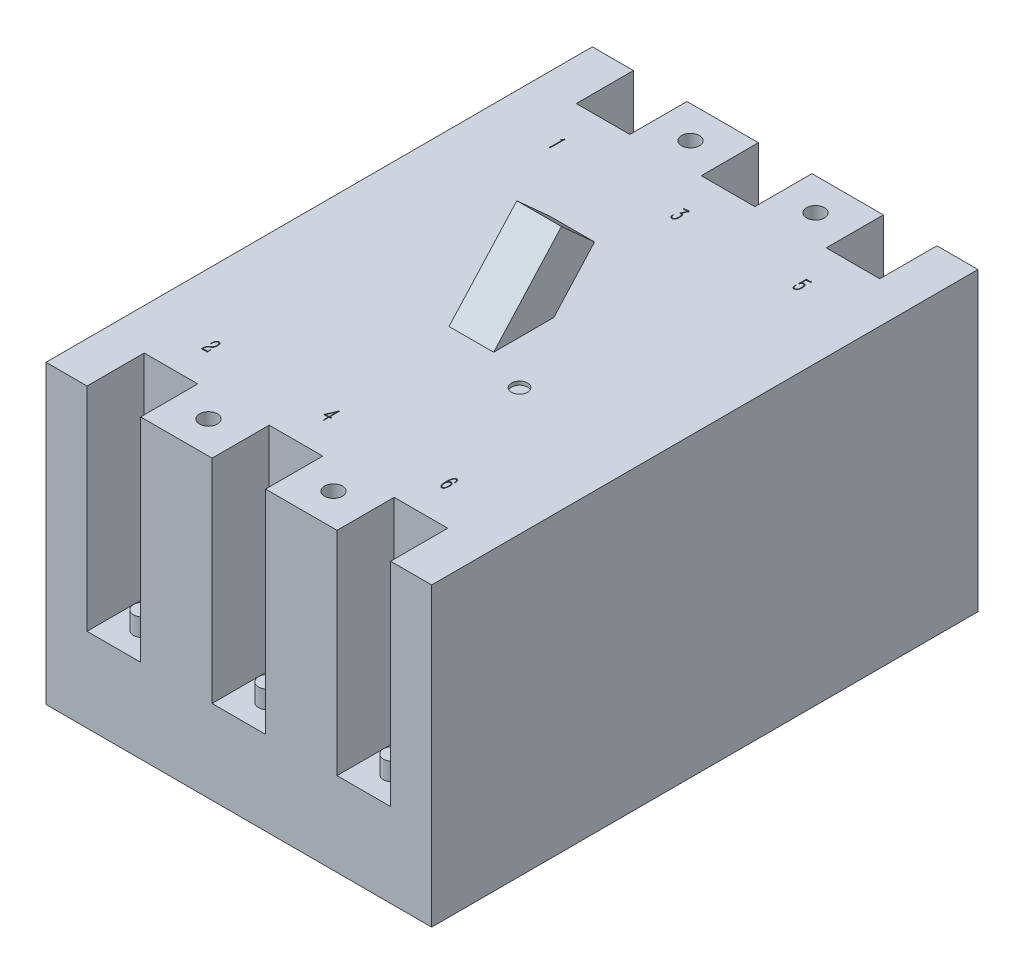
SolidWorks part; units mm, degrees
note: '?' marks a value the reader was unsure of.
ref_plane "前视基准面" through (0, 0, 0) normal (0, 0, 1) x (1, 0, 0)
ref_plane "上视基准面" through (0, 0, 0) normal (0, 1, 0) x (1, 0, 0)
ref_plane "右视基准面" through (0, 0, 0) normal (1, 0, 0) x (0, 0, -1)
sketch "草图1" plane through (0, 0, 0) normal (0, 1, 0) x (1, 0, 0)
  line L1 (-54, -76.5) -> (54, -76.5)
  line L2 (-54, -76.5) -> (-54, 76.5)
  line L3 (-54, 76.5) -> (54, 76.5)
  line L4 (54, -76.5) -> (54, 76.5)
  line L5 (-54, -76.5) -> (54, 76.5) construction
  line L6 (-54, 76.5) -> (54, -76.5) construction
  point P0 (0, 0)
  dimension "L" = 153
  dimension "W" = 108
extrude "凸台-拉伸1" add sketch "草图1" along normal blind 83
sketch "草图31" plane through (-5.5797, 0, -14.8647) normal (0, -1, 0) x (1, 0, 0)
  line L1 (-11.9203, 82.3647) -> (23.0797, 82.3647) construction
  line L2 (-11.9203, 82.3647) -> (-11.9203, -52.6353) construction
  line L3 (-11.9203, -52.6353) -> (23.0797, -52.6353) construction
  line L4 (23.0797, 82.3647) -> (23.0797, -52.6353) construction
  line L5 (-11.9203, 82.3647) -> (23.0797, -52.6353) construction
  line L6 (-11.9203, -52.6353) -> (23.0797, 82.3647) construction
  circle A0 centre (23.0797, -52.6353) radius 2.5
  circle A1 centre (-11.9203, -52.6353) radius 2.5
  circle A2 centre (23.0797, 82.3647) radius 2.5
  circle A3 centre (-11.9203, 82.3647) radius 2.5
  point P0 (5.5797, 14.8647)
  dimension "D1" = 5
  dimension "D2" = 35
  dimension "D3" = 135
extrude "切除-拉伸2" cut sketch "草图31" against normal through all
other "安装孔<1>"
sketch "草图3" [suppressed] plane through (0, 0, 0) normal (0, -1, 0) x (1, 0, 0)
  line L1 (-30, 50) -> (30, 50) construction
  line L2 (-30, 50) -> (-30, -50) construction
  line L3 (-30, -50) -> (30, -50) construction
  line L4 (30, 50) -> (30, -50) construction
  line L5 (-30, 50) -> (30, -50) construction
  line L6 (-30, -50) -> (30, 50) construction
  circle A0 centre (30, -50) radius 5
  circle A1 centre (-30, -50) radius 5
  circle A2 centre (30, 50) radius 5
  circle A3 centre (-30, 50) radius 5
  point P0 (0, 0)
  dimension "D1" = 10
  dimension "a" = 60
  dimension "b" = 100
sketch "草图4" plane through (0, 83, 0) normal (0, 1, 0) x (1, 0, 0)
  line L0 (0, 0) -> (0, 84.8308) construction
  line L1 (54, 76.5) -> (-54, 76.5) construction
  line L2 (0, 76.5) -> (7.5, 76.5)
  line L3 (0, 76.5) -> (0, 60.5)
  line L4 (0, 60.5) -> (7.5, 60.5)
  line L5 (7.5, 76.5) -> (7.5, 60.5)
  line L6 (17.5, 76.5) -> (17.5, 67.5) construction
  line L7 (27.5, 76.5) -> (42.5, 76.5)
  line L8 (27.5, 76.5) -> (27.5, 60.5)
  line L9 (27.5, 60.5) -> (42.5, 60.5)
  line L10 (42.5, 76.5) -> (42.5, 60.5)
  line L11 (7.5, 76.5) -> (27.5, 76.5) construction
  circle A1 centre (17.5, 67.5) radius 2.5 construction
  dimension "D1" = 15
  dimension "D2" = 16
  dimension "D3" = 15
extrude "切除-拉伸3" cut sketch "草图4" against normal offset from surface (59.5 mm away) 23.5 up to face at (-17.5, 0, 65)
sketch "草图33" plane through (0, 23.5, 0) normal (0, 1, 0) x (1, 0, 0)
  line L0 (42.5, 76.5) -> (27.5, 76.5) construction
  line L1 (42.5, 60.5) -> (42.5, 76.5) construction
  line L2 (0, 76.5) -> (0, 60.5) construction
  circle A0 centre (35, 68.5) radius 2.5
  circle A1 centre (0, 68.5) radius 2.5
  point P4 (35, 76.5)
  point P7 (42.5, 68.5)
  dimension "D1" = 5
extrude "凸台-拉伸2" add sketch "草图33" along normal blind 5
mirror "镜向1" about plane through (0, 0, 0) normal (1, 0, 0) of "凸台-拉伸2", "切除-拉伸3"
mirror "镜向2" about plane through (0, 0, 0) normal (0, 0, 1) of "凸台-拉伸2", "镜向1", "切除-拉伸3"
sketch "草图34" plane through (0, 0, 0) normal (1, 0, 0) x (0, 0, -1)
  line L0 (-11.3938, 83) -> (7.5959, 104)
  line L1 (-76.5, 83) -> (76.5, 83) construction
  line L2 (7.5959, 104) -> (16.8673, 95.6161)
  line L3 (16.8673, 95.6161) -> (5.459, 83)
  line L4 (5.459, 83) -> (-11.3938, 83)
  dimension "D1" = 12.5
  dimension "H" = 104
extrude "凸台-拉伸3" add sketch "草图34" along normal mid plane 12.5
sketch "草图35" plane through (0, 23.5, 0) normal (0, 1, 0) x (1, 0, 0)
  point P0 (-35, 68.5)
  point P1 (0, 68.5)
  point P3 (35, 68.5)
  point P5 (35, -68.5)
  point P7 (0, -68.5)
  point P9 (-35, -68.5)
sketch "草图36" plane through (0, 83, 0) normal (0, 1, 0) x (1, 0, 0)
  line L0 (-36.641, 45.6036) -> (34.2686, 45.6036) construction
  text T0 "135" font "汉仪长仿宋体" height in points 18
extrude "切除-拉伸4" cut sketch "草图36" against normal blind 1
sketch "草图37" plane through (0, 83, 0) normal (0, 1, 0) x (1, 0, 0)
  line L0 (-35.8502, -51.9301) -> (32.9506, -51.9301) construction
  circle A0 centre (18.4523, -16.3435) radius 2.2522
  text T0 "246\r\n" font "汉仪长仿宋体" height in points 18
extrude "切除-拉伸6" cut sketch "草图37" against normal blind 1
sketch "0_0_Point" plane through (0, 23.5, 0) normal (0, 1, 0) x (1, 0, 0)
  point P0 (-35, 68.5)
other "0_0" parameters "直径"=2, "端头长度"=2
ref_axis "基准轴1" through (-35, 33.5, -68.5) along (0, -1, 0)?
sketch "0_1_Point" plane through (0, 23.5, 0) normal (0, 1, 0) x (1, 0, 0)
  point P0 (-35, -68.5)
other "0_1" parameters "直径"=2, "端头长度"=2
ref_axis "基准轴2" through (-35, 33.5, 68.5) along (0, -1, 0)?
sketch "1_0_Point" plane through (0, 23.5, 0) normal (0, 1, 0) x (1, 0, 0)
  point P0 (0, 68.5)
other "1_0" parameters "直径"=2, "端头长度"=2
ref_axis "基准轴3" through (0, 33.5, -68.5) along (0, -1, 0)?
sketch "1_1_Point" plane through (0, 23.5, 0) normal (0, 1, 0) x (1, 0, 0)
  point P0 (0, -68.5)
other "1_1" parameters "直径"=2, "端头长度"=2
ref_axis "基准轴4" through (0, 33.5, 68.5) along (0, -1, 0)?
sketch "2_0_Point" plane through (0, 23.5, 0) normal (0, 1, 0) x (1, 0, 0)
  point P0 (35, 68.5)
other "2_0" parameters "直径"=2, "端头长度"=2
ref_axis "基准轴5" through (35, 33.5, -68.5) along (0, -1, 0)?
sketch "2_1_Point" plane through (0, 23.5, 0) normal (0, 1, 0) x (1, 0, 0)
  point P0 (35, -68.5)
other "2_1" parameters "直径"=2, "端头长度"=2
ref_axis "基准轴6" through (35, 33.5, 68.5) along (0, -1, 0)?
